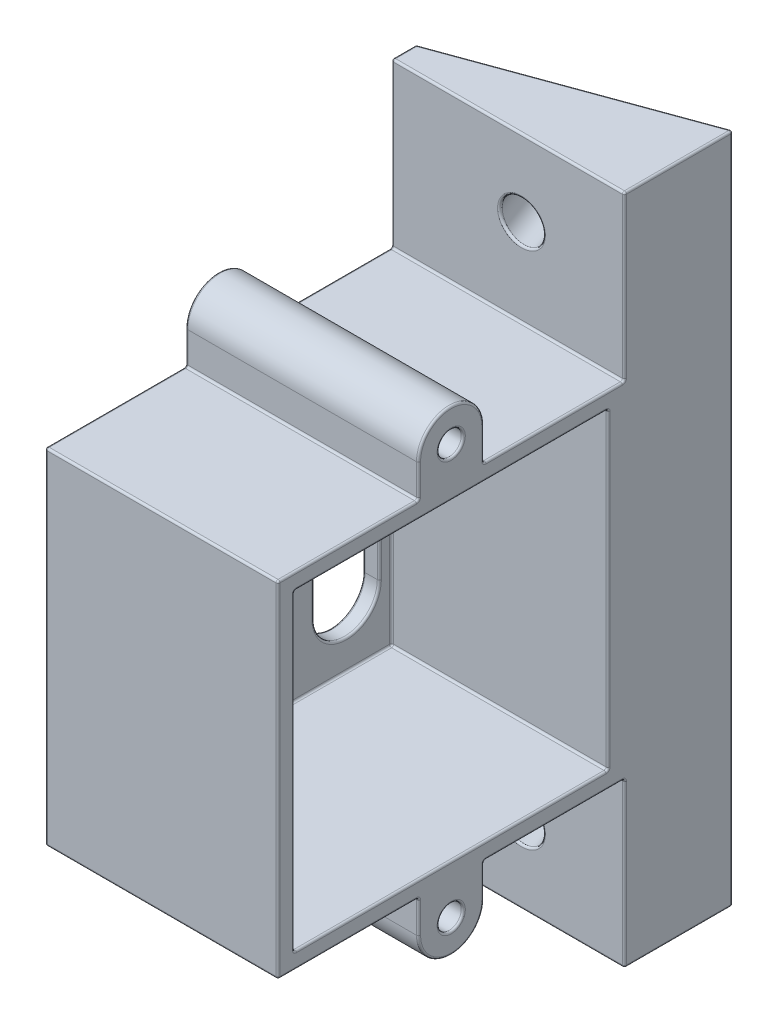
SolidWorks part; units mm, degrees
ref_plane "Front Plane" through (0, 0, 0) normal (1, 0, 0) x (0, 1, 0)
ref_plane "Top Plane" through (0, 0, 0) normal (0, 0, 1) x (0, 1, 0)
ref_plane "Right Plane" through (0, 0, 0) normal (0, 1, 0) x (-1, 0, 0)
sketch "Sketch1" plane through (0, 0, 0) normal (1, 0, 0) x (0, 1, 0)
  line L1 (-19.1, 19.2) -> (19.1, 19.2)
  line L2 (-19.1, 19.2) -> (-19.1, -19.2)
  line L3 (-19.1, -19.2) -> (19.1, -19.2)
  line L4 (19.1, 19.2) -> (19.1, -19.2)
  line L5 (-19.1, 19.2) -> (19.1, -19.2) construction
  line L6 (-19.1, -19.2) -> (19.1, 19.2) construction
  line L7 (-21.1, 21.2) -> (21.1, 21.2)
  line L8 (-21.1, 21.2) -> (-21.1, 4)
  line L9 (-21.1, -21.2) -> (21.1, -21.2)
  line L10 (21.1, 21.2) -> (21.1, 4)
  line L11 (-21.1, 21.2) -> (21.1, -21.2) construction
  line L12 (-21.1, -21.2) -> (21.1, 21.2) construction
  line L14 (0, 31.084) -> (0, -25.7946) construction
  line L17 (-21.1, -4) -> (-21.1, -21.2)
  line L18 (21.1, -4) -> (21.1, -21.2)
  line L19 (-25.1, 4) -> (-21.1, 4)
  line L20 (-25.1, -4) -> (-21.1, -4)
  line L21 (25.1, -4) -> (21.1, -4)
  line L22 (25.1, 4) -> (21.1, 4)
  circle A0 centre (-25.1, 0) radius 1.475
  circle A2 centre (25.1, 0) radius 1.475
  arc A4 (-25.1, 4) -> (-25.1, -4) centre (-25.1, 0) ccw
  arc A5 (25.1, 4) -> (25.1, -4) centre (25.1, 0) cw
  point P0 (0, 0)
  point P6 (0, 0)
  dimension "D5" = 2.95
  dimension "D1" = 38.4
  dimension "D2" = 38.2
  dimension "D3" = 42.2
  dimension "D4" = 42.4
  dimension "D6" = 4
extrude "Boss-Extrude1" add sketch "Sketch1" along normal blind 26.5
sketch "Sketch2" plane through (0, 0, 0) normal (-1, 0, 0) x (0, -1, 0)
  line L1 (-21.1, 21.2) -> (21.1, 21.2)
  line L2 (-21.1, 21.2) -> (-21.1, 4)
  line L3 (-21.1, -21.2) -> (21.1, -21.2)
  line L4 (21.1, 21.2) -> (21.1, 4)
  line L7 (-25.1, 4) -> (-21.1, 4)
  line L11 (-25.1, -4) -> (-21.1, -4)
  line L12 (-21.1, -4) -> (-21.1, -21.2)
  line L13 (21.1, -4) -> (21.1, -21.2)
  line L14 (0, 23.9961) -> (0, -25.7946) construction
  line L15 (0, 31.084) -> (0, -25.7946) construction
  line L16 (25.1, -4) -> (21.1, -4)
  line L17 (25.1, 4) -> (21.1, 4)
  arc A4 (-25.1, 4) -> (-25.1, -4) centre (-25.1, 0) ccw
  arc A6 (25.1, 4) -> (25.1, -4) centre (25.1, 0) cw
extrude "Boss-Extrude4" add sketch "Sketch2" along normal blind 2
sketch "Sketch3" plane through (-2, 0, 0) normal (-1, 0, 0) x (0, -1, 0)
  line L0 (-11.5, -13.7) -> (11.5, -13.7) construction
  line L1 (-11.5, -9.7) -> (11.5, -9.7)
  line L2 (-11.5, -17.7) -> (11.5, -17.7)
  line L3 (21.1, -21.2) -> (-21.1, -21.2) construction
  arc A0 (-11.5, -9.7) -> (-11.5, -17.7) centre (-11.5, -13.7) ccw
  arc A1 (11.5, -17.7) -> (11.5, -9.7) centre (11.5, -13.7) ccw
  point P2 (0, -13.7)
  dimension "D1" = 7.5
extrude "Cut-Extrude1" cut sketch "Sketch3" against normal blind 2
sketch "Sketch9" plane through (0, 21.1, 0) normal (0, 1, 0) x (-1, 0, 0)
  line L0 (2, -21.2) -> (2, -24.2)
  line L2 (-26.5, -34.5732) -> (-26.5, -21.2)
  line L3 (-26.5, -21.2) -> (2, -21.2)
  line L4 (-26.5, -34.5732) -> (2, -24.2)
  dimension "D1" = 3
extrude "Boss-Extrude7" add sketch "Sketch9" against normal blind 62.2 and the other way blind 20
sketch "Sketch10" plane through (-8.0117, 0, -22.0119) normal (-0.342, 0, -0.9397) x (0.9397, 0, -0.342)
  line L0 (6.3975, -41.1) -> (6.3975, 41.1) construction
  circle A0 centre (20.3975, 31.75) radius 2.5
  circle A1 centre (20.3975, -31.75) radius 2.5
  point P8 (51.8232, -25.0901)
  dimension "D1" = 5
  dimension "D2" = 5
  dimension "D3" = 14
  dimension "D4" = 14
  dimension "D5" = 31.75
  dimension "D6" = 31.75
extrude "Cut-Extrude3" cut sketch "Sketch10" against normal blind 20
fillet "Fillet4" radius 0.25 72 edges at (8.8065, 31.75, -28.1332) (8.8065, -31.75, -28.1332) (11.33, 31.75, -21.2) (11.33, -31.75, -21.2) (12.25, -41.1, -21.2) (26.5, -41.1, -27.8866) (12.25, -41.1, -29.3866) (-2, -41.1, -22.7) (12.25, 41.1, -21.2) (26.5, 41.1, -27.8866) (12.25, 41.1, -29.3866) (-2, 41.1, -22.7) (-2, -31.1, -21.2) (-2, 31.1, -21.2) (-2, 0, -24.2) (26.5, 0, -34.5732) (26.5, -31.1, -21.2) (26.5, 31.1, -21.2) (-2, 15.5, -13.7) (-2, 0, -17.7) (-2, -15.5, -13.7) (-2, 0, -9.7) (0, 15.5, -13.7) (0, 0, -17.7) (0, -15.5, -13.7) (0, 0, -9.7) (-2, 21.1, 12.6) (-2, 23.1, 4) (-2, 29.1, 0) (-2, 23.1, -4) (-2, 21.1, -12.6) (-2, -21.1, -12.6) (-2, -23.1, -4) (-2, -29.1, 0) (-2, -23.1, 4) (-2, -21.1, 12.6) (-2, 0, 21.2) (0, 25.1, 1.475) (26.5, 25.1, 1.475) (0, -25.1, -1.475) (26.5, -25.1, -1.475) (0, 19.1, 0) (0, 0, 19.2) (0, -19.1, 0) (0, 0, -19.2) (26.5, 19.1, 0) (26.5, 0, 19.2) (26.5, -19.1, 0) (26.5, 0, -19.2) (13.25, 19.1, -19.2) (13.25, -19.1, -19.2) (13.25, -19.1, 19.2) (13.25, 19.1, 19.2) (26.5, 21.1, -12.6) (26.5, 23.1, -4) (26.5, 29.1, 0) (26.5, 23.1, 4) (26.5, 21.1, 12.6) (26.5, 0, 21.2) (26.5, -21.1, 12.6) (26.5, -23.1, 4) (26.5, -29.1, 0) (26.5, -23.1, -4) (26.5, -21.1, -12.6) (12.25, 21.1, -21.2) (12.25, -21.1, -21.2) (12.25, -21.1, -4) (12.25, -21.1, 4) (12.25, -21.1, 21.2) (12.25, 21.1, 21.2) (12.25, 21.1, 4) (12.25, 21.1, -4)
